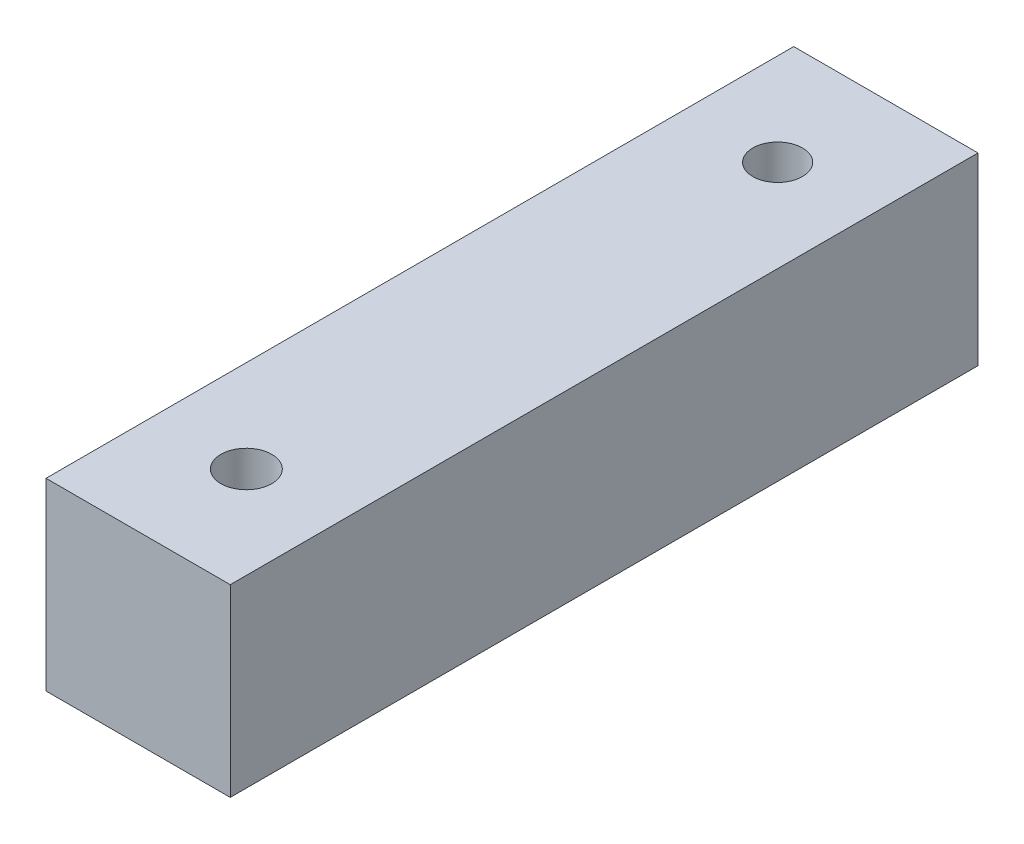
SolidWorks part; units mm, degrees
ref_plane "Front Plane" through (0, 0, 0) normal (0, 0, 1) x (1, 0, 0)
ref_plane "Top Plane" through (0, 0, 0) normal (0, 1, 0) x (1, 0, 0)
ref_plane "Right Plane" through (0, 0, 0) normal (1, 0, 0) x (0, 0, -1)
sketch "Sketch1" plane through (0, 0, 0) normal (0, 0, 1) x (1, 0, 0)
  line L1 (-6.35, -6.35) -> (6.35, -6.35)
  line L2 (-6.35, -6.35) -> (-6.35, 6.35)
  line L3 (-6.35, 6.35) -> (6.35, 6.35)
  line L4 (6.35, -6.35) -> (6.35, 6.35)
  line L5 (-6.35, -6.35) -> (6.35, 6.35) construction
  line L6 (-6.35, 6.35) -> (6.35, -6.35) construction
  point P0 (0, 0)
  dimension "D1" = 12.7
  dimension "D2" = 12.7
extrude "Boss-Extrude1" add sketch "Sketch1" along normal blind 51.5391
sketch "Sketch2" plane through (0, -6.35, 0) normal (0, -1, 0) x (1, 0, 0)
  circle A0 centre (0, 44.0804) radius 1.7545
  circle A1 centre (0, 7.4612) radius 1.7101
  dimension "D1" = 3.5091
  dimension "D2" = 3.4201
extrude "Cut-Extrude1" cut sketch "Sketch2" against normal through all
